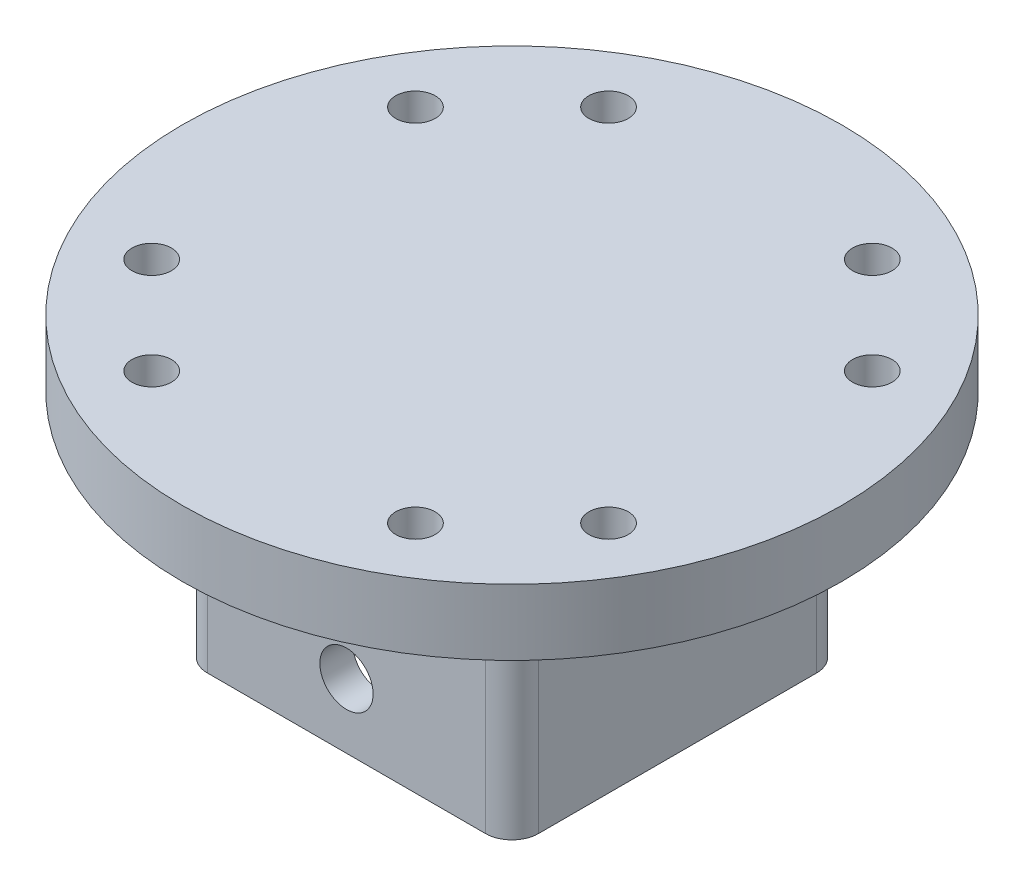
SolidWorks part; units mm, degrees
ref_plane "Front Plane" through (0, 0, 0) normal (0, 0, 1) x (1, 0, 0)
ref_plane "Top Plane" through (0, 0, 0) normal (0, 1, 0) x (1, 0, 0)
ref_plane "Right Plane" through (0, 0, 0) normal (1, 0, 0) x (0, 0, -1)
sketch "Sketch1" plane through (0, 0, 0) normal (0, 1, 0) x (1, 0, 0)
  circle A0 centre (0, 0) radius 31.75 construction
  circle A1 centre (0, 0) radius 15.9385 construction
  circle A2 centre (0, 0) radius 12.7635 construction
  dimension "D1" = 63.5
  dimension "D2" = 25.527
  dimension "D3" = 3.175
sketch "Sketch6" plane through (0, 0, 0) normal (0, 0, 1) x (1, 0, 0)
  line L0 (0, -18.7832) -> (0, 8.1093) construction
sketch "Sketch2" plane through (0, 0, 0) normal (0, 1, 0) x (1, 0, 0)
  circle A0 centre (0, 0) radius 31.75 construction
  circle A1 centre (0, 0) radius 31.75
extrude "Boss-Extrude1" add sketch "Sketch2" along normal blind 6.35
sketch "Sketch3" plane through (0, 0, 0) normal (0, 1, 0) x (1, 0, 0)
  line L0 (15.9385, 15.9385) -> (15.9385, -15.9385)
  line L1 (15.9385, -15.9385) -> (-15.9385, -15.9385)
  line L2 (-15.9385, -15.9385) -> (-15.9385, 15.9385)
  line L3 (-15.9385, 15.9385) -> (15.9385, 15.9385)
  circle A2 centre (0, 0) radius 15.9385 construction
extrude "Boss-Extrude2" add sketch "Sketch3" against normal blind 22.225
sketch "Sketch4" plane through (0, 0, 0) normal (0, 1, 0) x (1, 0, 0)
  line L0 (12.7635, 12.7635) -> (12.7635, -12.7635)
  line L1 (12.7635, -12.7635) -> (-12.7635, -12.7635)
  line L2 (-12.7635, -12.7635) -> (-12.7635, 12.7635)
  line L3 (-12.7635, 12.7635) -> (12.7635, 12.7635)
  circle A2 centre (0, 0) radius 12.7635 construction
extrude "Cut-Extrude1" cut sketch "Sketch4" against normal through all
sketch "Sketch5" plane through (0, 0, 0) normal (0, 1, 0) x (1, 0, 0)
  line L0 (0, 0) -> (37.5473, 0) construction
  line L1 (0, 0) -> (21.997, 12.7) construction
  circle A1 centre (21.997, 12.7) radius 1.9
  circle A2 centre (21.997, -12.7) radius 1.9
  dimension "D5" = 3.8
  dimension "D2" = 30
  dimension "D3" = 25.4
extrude "Cut-Extrude2" cut sketch "Sketch5" along normal through all
sketch "Sketch7" plane through (0, 0, 0) normal (0, 0, 1) x (1, 0, 0)
  line L0 (0, -18.7832) -> (0, 8.1093) construction
  circle A0 centre (0, -16.002) radius 2.5635
  dimension "D1" = 5.127
  dimension "D2" = 16.002
extrude "Cut-Extrude3" cut sketch "Sketch7" against normal through all both and the other way through all
pattern_circular "CirPattern2" count 4 over 360 about axis through (0, -18.7832, 0) along (0, 1, 0) of "Cut-Extrude2" reverse direction yes
fillet "Fillet2" radius 2.54 4 edges at (-15.9385, -11.1125, 15.9385) (15.9385, -11.1125, 15.9385) (15.9385, -11.1125, -15.9385) (-15.9385, -11.1125, -15.9385)
fillet "Fillet3" radius 2.54 8 edges at (15.1946, 0, -15.1946) (15.9385, 0, 0) (15.1946, 0, 15.1946) (0, 0, 15.9385) (-15.1946, 0, 15.1946) (-15.9385, 0, 0) (-15.1946, 0, -15.1946) (0, 0, -15.9385)
equation "\"tightTol\"= 0.005in"
equation "\"normTol\"= 0.01in"
equation "\"looseTol\"= 0.02in"
equation "\"D2@Sketch1\"=\"tightTol\"+1.000000in"
equation "\"D5@Sketch5\"=3.8mm"
equation "\"D1@Sketch7\"=\"tightTol\"+5mm"
equation "\"D2@Sketch7\"=\"tightTol\"+0.625000in"
